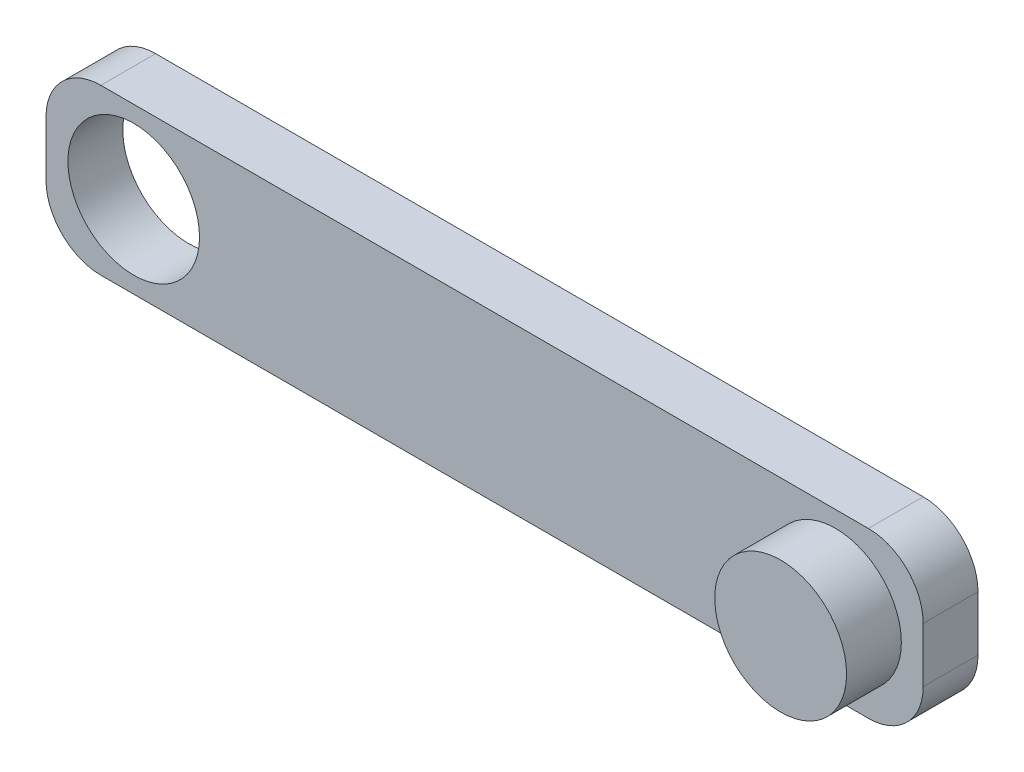
SolidWorks part; units mm, degrees
ref_plane "前视基准面" through (0, 0, 0) normal (0, 0, 1) x (1, 0, 0)
ref_plane "上视基准面" through (0, 0, 0) normal (0, 1, 0) x (1, 0, 0)
ref_plane "右视基准面" through (0, 0, 0) normal (1, 0, 0) x (0, 0, -1)
sketch "草图1" plane through (0, 0, 0) normal (0, 0, 1) x (1, 0, 0)
  line L0 (5, 15) -> (5, 0)
  line L1 (5, 0) -> (75, 0)
  line L2 (0, 5) -> (0, 10)
  line L3 (5, 15) -> (75, 15)
  line L4 (80, 5) -> (80, 10)
  line L5 (0, 7.5) -> (5, 7.5)
  line L6 (5, 7.5) -> (80, 7.5)
  line L7 (75, 15) -> (75, 7.5)
  line L8 (75, 7.5) -> (75, 0)
  line L9 (5, 7.5) -> (8, 7.5)
  line L10 (75, 7.5) -> (72, 7.5)
  arc A0 (75, 0) -> (80, 5) centre (75, 5) ccw
  arc A1 (75, 15) -> (80, 10) centre (75, 10) cw
  arc A2 (5, 0) -> (0, 5) centre (5, 5) cw
  arc A3 (0, 10) -> (5, 15) centre (5, 10) cw
  circle A4 centre (8, 7.5) radius 6
  circle A5 centre (8, 7.5) radius 6
  circle A6 centre (72, 7.5) radius 6.0107
  point P11 (0, 0)
  dimension "D1" = 5
  dimension "D5" = 3
  dimension "D2" = 70
  dimension "D3" = 15
  dimension "D4" = 3
extrude "凸台-拉伸1" add sketch "草图1" along normal blind 5 contours A6 L6 A4 L0 L1 L8 | A4 L5 L2 A2 L0 | A4 L0 A3 L2 L5 | A6 L7 L3 L0 A4 L6 | A6 L6 L4 A1 L7 | A6 L8 A0 L4 L6 region at (39.9909, 11.4762, 0) region at (2.186, 11.4792, 0) region at (77.8167, 11.4827, 0) region at (39.9909, 3.5238, 0) region at (2.186, 3.5208, 0) region at (77.8167, 3.5173, 0)
extrude "凸台-拉伸2" add sketch "草图1<3>" along normal blind 10 contours L7 A6 L6 | L6 A6 L7 | L8 A6 L6 | L6 A6 L8 region at (76.2346, 9.5402, 0) region at (70.9678, 10.1755, 0) region at (70.9678, 4.8245, 0) region at (76.2346, 5.4598, 0)
sketch "草图1<3>" plane through (0, 0, 0) normal (0, 0, 1) x (1, 0, 0) same geometry as "草图1"
